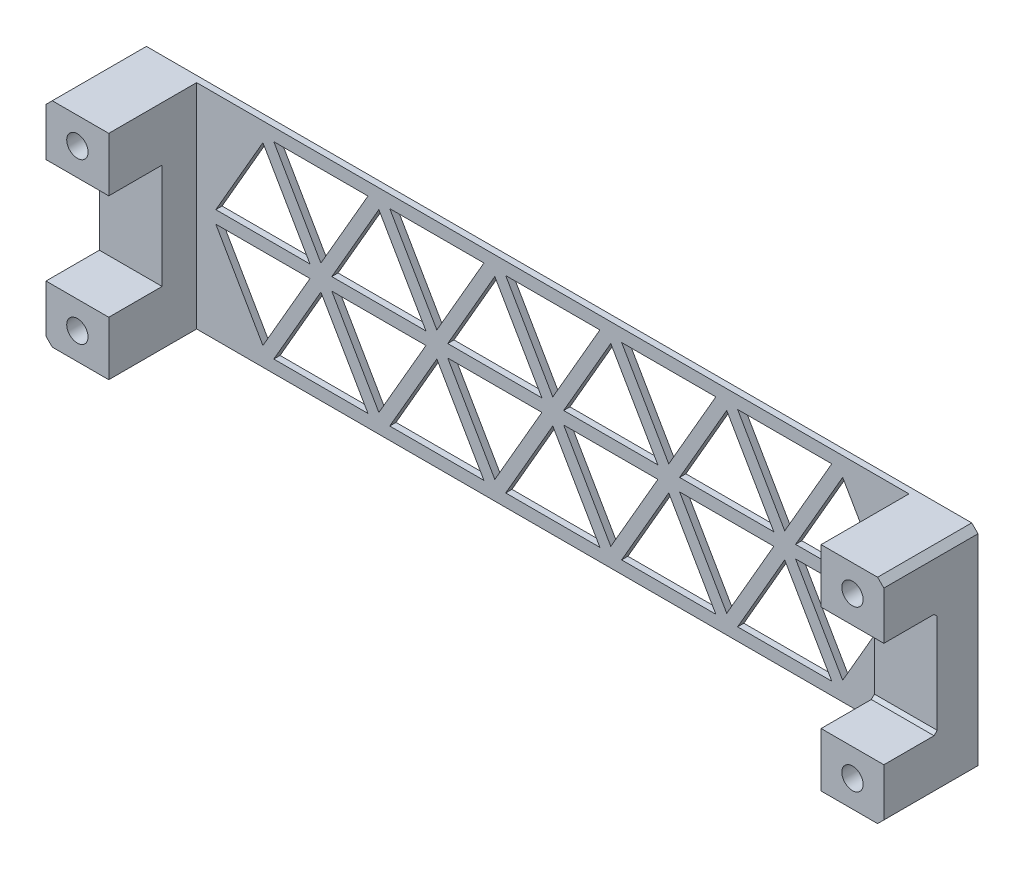
SolidWorks part; units mm, degrees
material "ABS"
ref_plane "Front Plane" through (0, 0, 0) normal (0, 0, 1) x (1, 0, 0)
ref_plane "Top Plane" through (0, 0, 0) normal (0, 1, 0) x (1, 0, 0)
ref_plane "Right Plane" through (0, 0, 0) normal (1, 0, 0) x (0, 0, -1)
ref_axis "X" through (-88.99, 0, 0) along (1, 0, 0)
ref_axis "Y" through (0, 55, 0) along (0, -1, 0)
ref_axis "Z" through (0, 0, -88.99) along (0, 0, 1)
sketch "Sketch1" plane through (0, 0, 0) normal (0, 0, 1) x (1, 0, 0)
  line L1 (-66.75, 17) -> (66.75, 17)
  line L2 (-66.75, 17) -> (-66.75, -17)
  line L3 (-66.75, -17) -> (66.75, -17)
  line L4 (66.75, 17) -> (66.75, -17)
  line L5 (-66.75, 17) -> (66.75, -17) construction
  line L6 (-66.75, -17) -> (66.75, 17) construction
  point P0 (0, 0)
  dimension "D1" = 34
  dimension "D2" = 133.5
extrude "Boss-Extrude1" add sketch "Sketch1" along normal blind 1
sketch "Sketch2" plane through (0, 0, 0) normal (0, 0, 1) x (1, 0, 0)
  line L0 (66.75, -17.125) -> (66.75, -8.375) construction
  line L1 (56.75, -8.375) -> (56.75, -17.125) construction
  line L2 (66.75, 8.375) -> (66.75, 17.125) construction
  line L3 (56.75, 17.125) -> (56.75, 8.375) construction
  line L4 (66.75, 8.375) -> (66.75, -8.375) construction
  line L5 (66.75, -8.375) -> (56.75, -8.375) construction
  line L6 (66.75, 8.375) -> (56.75, 8.375) construction
  line L7 (56.75, 8.375) -> (56.75, -8.375) construction
  line L8 (66.75, -17) -> (66.75, -8.375)
  line L9 (56.75, -8.375) -> (56.75, -17)
  line L10 (66.75, 8.375) -> (66.75, 17)
  line L11 (56.75, 17) -> (56.75, 8.375)
  line L12 (66.75, 8.375) -> (66.75, -8.375)
  line L13 (66.75, -8.375) -> (56.75, -8.375)
  line L14 (66.75, 8.375) -> (56.75, 8.375)
  line L15 (56.75, 8.375) -> (56.75, -8.375)
  line L16 (56.75, 17) -> (66.75, 17)
  line L17 (66.75, 17) -> (-66.75, 17) construction
  line L18 (56.75, -17) -> (66.75, -17)
  line L19 (-66.75, -17) -> (66.75, -17) construction
  circle A0 centre (61.75, -12.75) radius 2.5 construction
  circle A1 centre (61.75, 12.75) radius 2.5 construction
  circle A2 centre (61.75, -12.75) radius 2.5 construction
  circle A3 centre (61.75, 12.75) radius 2.5 construction
extrude "Boss-Extrude2" add sketch "Sketch2" along normal up to surface (15 mm away) contours L16 L11 L14 L10 A3 | L9 L18 L8 L13 A2 region at (61.75, -12.6875, 0) region at (61.75, 12.6875, 0)
extrude "Boss-Extrude3" add sketch "Sketch2<3>" along normal offset from surface (6.5 mm away) 8.5 contours L14 L15 L13 L12 region at (61.75, 0, 0)
sketch "Sketch2<3>" plane through (0, 0, 0) normal (0, 0, 1) x (1, 0, 0) same geometry as "Sketch2"
sketch "Sketch5" plane through (0, 0, 0) normal (0, 0, -1) x (-1, 0, 0)
  point P0 (-61.75, 12.75)
  point P3 (-61.75, -12.75)
hole_wizard "CBORE for M3 SHCS1" positions "Sketch5" profile "Sketch4" counterbore size "M3" standard "ANSI Metric" end condition through all
sketch "Sketch4" plane through (61.75, 12.75, 0) normal (1, 0, 0) x (0, 1, 0)
  line L0 (0, 0) -> (0, 15)
  line L1 (0, 15) -> (1.7, 15)
  line L3 (1.7, 15) -> (1.7, 3)
  line L4 (1.7, 3) -> (3.25, 3)
  line L5 (3.25, 3) -> (3.25, 0)
  line L7 (3.25, 0) -> (0, 0)
  line L11 (0, -6.35) -> (0, 107.95) construction
  dimension "Thru Hole Dia." = 3.4
  dimension "Thru Hole Depth" = 15
  dimension "C'Bore Dia." = 6.5
  dimension "C'Bore Depth" = 3
chamfer "Chamfer1" distance 0.5 angle 45 2 edges at (61.75, -8.375, 6.5) (61.75, 8.375, 6.5)
mirror "Mirror1" about plane through (0, 0, 0) normal (1, 0, 0) of "CBORE for M3 SHCS1", "Boss-Extrude3", "Boss-Extrude2"
chamfer "Chamfer2" distance 0.5 angle 45 4 edges at (-65, -12.75, 0) (-65, 12.75, 0) (58.5, -12.75, 0) (58.5, 12.75, 0)
sketch "Sketch6" plane through (0, 0, 0) normal (0, 0, 1) x (1, 0, 0)
  line L8 (-8.6603, 15) -> (0, 0) construction
  line L9 (8.6603, -15) -> (17.3205, 0)
  line L10 (17.3205, 0) -> (8.6603, 15)
  line L11 (8.6603, 15) -> (-8.6603, 15)
  line L12 (-8.6603, 15) -> (-17.3205, 0)
  line L13 (-17.3205, 0) -> (-8.6603, -15)
  line L14 (-8.6603, -15) -> (8.6603, -15)
  line L15 (0, 0) -> (8.6603, 15) construction
  line L16 (0, 0) -> (17.3205, 0) construction
  line L17 (0, 0) -> (8.6603, -15) construction
  line L18 (0, 0) -> (-8.6603, -15) construction
  line L19 (0, 0) -> (-17.3205, 0) construction
  line L20 (-9.2376, 14) -> (7.5056, -15)
  line L21 (9.2376, -14) -> (-7.5056, 15)
  line L22 (7.5056, 15) -> (-9.2376, -14)
  line L23 (-7.5056, -15) -> (9.2376, 14)
  line L24 (16.7432, 1) -> (-16.7432, 1)
  line L25 (-16.7432, -1) -> (16.7432, -1)
  circle A0 centre (0, 0) radius 15 construction
  dimension "D6" = 30
  dimension "D5" = 2
extrude "Cut-Extrude1" cut sketch "Sketch6" along normal through all contours L22 L11 L21 | L24 L20 L12 | L25 L13 L22 | L24 L10 L23 | L25 L21 L9 | L23 L14 L20 region at (9.2376, -5.3333, 0) region at (0, -10.6667, 0) region at (9.2376, 5.3333, 0) region at (-9.2376, -5.3333, 0) region at (0, 10.6667, 0) region at (-9.2376, 5.3333, 0)
pattern_linear "LPattern1" count 3 spacing 18.475 along (-1, 0, 0) of "Cut-Extrude1"
mirror "Mirror2" about plane through (0, 0, 0) normal (1, 0, 0) of "LPattern1"
chamfer "Chamfer3" distance 1 angle 45 4 edges at (-66.75, -17, 7.5) (-66.75, 17, 7.5) (66.75, -17, 7.5) (66.75, 17, 7.5)
